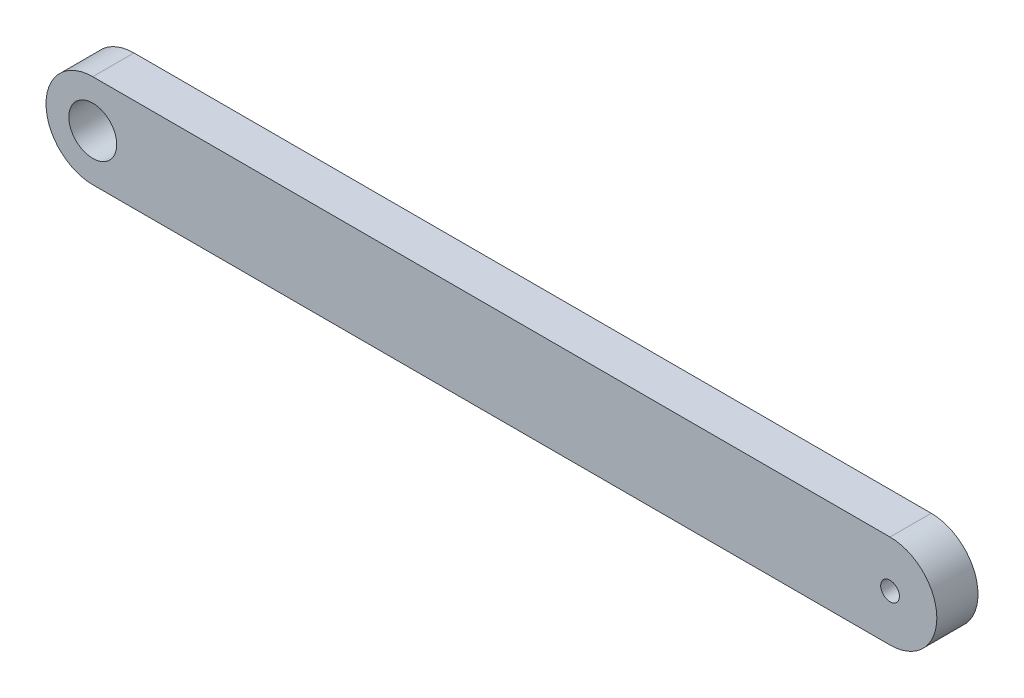
SolidWorks part; units mm, degrees
ref_plane "Front Plane" through (0, 0, 0) normal (0, 0, 1) x (1, 0, 0)
ref_plane "Top Plane" through (0, 0, 0) normal (0, 1, 0) x (1, 0, 0)
ref_plane "Right Plane" through (0, 0, 0) normal (1, 0, 0) x (0, 0, -1)
sketch "Sketch1" plane through (0, 0, 0) normal (0, 0, 1) x (1, 0, 0)
  line L0 (0, 0) -> (53.25, 0) construction
  line L1 (0, 3.125) -> (53.25, 3.125)
  line L2 (0, -3.125) -> (53.25, -3.125)
  arc A0 (0, 3.125) -> (0, -3.125) centre (0, 0) ccw
  arc A1 (53.25, -3.125) -> (53.25, 3.125) centre (53.25, 0) ccw
  circle A2 centre (0, 0) radius 1.6
  circle A3 centre (53.25, 0) radius 0.625
  point P3 (26.625, 0)
  dimension "D2" = 3.2
  dimension "D3" = 3.125
  dimension "D4" = 1.25
  dimension "D1" = 53.25
extrude "Boss-Extrude1" add sketch "Sketch1" along normal blind 2.75
